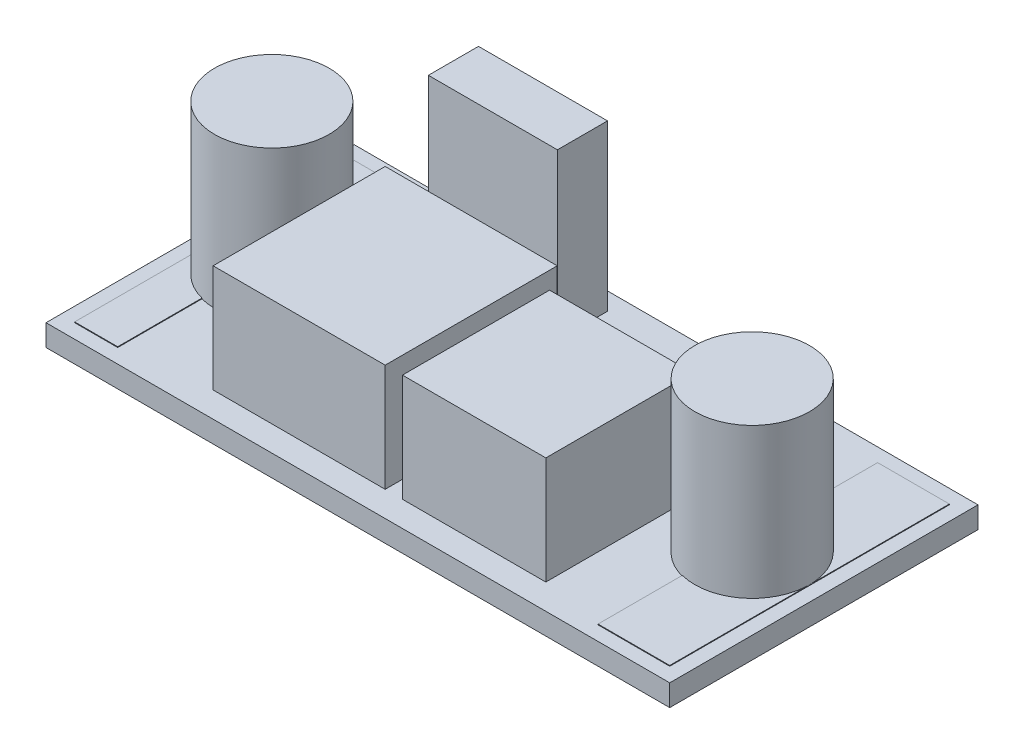
SolidWorks part; units mm, degrees
ref_plane "Спереди" through (0, 0, 0) normal (0, 0, 1) x (1, 0, 0)
ref_plane "Сверху" through (0, 0, 0) normal (0, 1, 0) x (1, 0, 0)
ref_plane "Справа" through (0, 0, 0) normal (1, 0, 0) x (0, 0, -1)
sketch "Эскиз1" plane through (0, 0, 0) normal (0, 1, 0) x (1, 0, 0)
  line L1 (0, 10.75) -> (-43.5, 10.75)
  line L2 (0, 10.75) -> (0, -10.75)
  line L3 (0, -10.75) -> (-43.5, -10.75)
  line L4 (-43.5, 10.75) -> (-43.5, -10.75)
  point P4 (0, 0)
  dimension "D1" = 21.5
  dimension "D2" = 43.5
extrude "Бобышка-Вытянуть1" add sketch "Эскиз1" along normal blind 1.5
sketch "Эскиз6" plane through (0, 0, 0) normal (0, 1, 0) x (1, 0, 0)
  line L0 (-43.5, -10.75) -> (0, -10.75) construction
  line L1 (0, 10.75) -> (-7, 10.75) construction
  line L2 (0, 10.75) -> (0, -10.75) construction
  line L3 (0, -10.75) -> (-7, -10.75) construction
  line L4 (-7, 10.75) -> (-7, -10.75) construction
  line L5 (-1, 9.75) -> (-6, 9.75)
  line L6 (-43.5, 10.75) -> (-38.5, 10.75) construction
  line L7 (-43.5, 10.75) -> (-43.5, -10.75) construction
  line L8 (-43.5, -10.75) -> (-38.5, -10.75) construction
  line L9 (-38.5, 10.75) -> (-38.5, -10.75) construction
  line L10 (-6, 9.75) -> (-6, -9.75)
  line L11 (-1, -9.75) -> (-6, -9.75)
  line L12 (-1, 9.75) -> (-1, -9.75)
  line L13 (-42.5, 9.75) -> (-39.5, 9.75)
  line L14 (-39.5, 9.75) -> (-39.5, -9.75)
  line L15 (-42.5, -9.75) -> (-39.5, -9.75)
  line L16 (-42.5, 9.75) -> (-42.5, -9.75)
  dimension "D1" = 7
  dimension "D2" = 5
  dimension "D3" = 1
extrude "Бобышка-Вытянуть4" add sketch "Эскиз6" along normal offset from surface (1.55 mm away) 0.05 up to face at (-21.75, 1.5, 0) offset beyond the face yes
sketch "Эскиз4" plane through (0, 0, 0) normal (0, 1, 0) x (1, 0, 0)
  line L9 (0, 0) -> (-43.5, 0) construction
  line L10 (-43.5, 10.75) -> (-43.5, -10.75) construction
  line L15 (-33.6103, 9.5227) -> (-24.6103, 9.5227)
  line L16 (-33.6103, 3.0151) -> (-21.6103, 3.0151)
  line L17 (-33.6103, 3.0151) -> (-33.6103, -8.9849)
  line L18 (-33.6103, -8.9849) -> (-21.6103, -8.9849)
  line L19 (-21.6103, 3.0151) -> (-21.6103, -8.9849)
  line L20 (-20.4056, 1.2772) -> (-10.4056, 1.2772)
  line L21 (-20.4056, 1.2772) -> (-20.4056, -8.9849)
  line L22 (-20.4056, -8.9849) -> (-10.4056, -8.9849)
  line L23 (-10.4056, 1.2772) -> (-10.4056, -8.9849)
  line L24 (-33.6103, 9.5227) -> (-33.6103, 6.0273)
  line L25 (-33.6103, 6.0273) -> (-24.6103, 6.0273)
  line L26 (-24.6103, 9.5227) -> (-24.6103, 6.0273)
  line L28 (-1, -9.75) -> (-1, 9.75) construction
  line L29 (-42.5, 9.75) -> (-42.5, -9.75) construction
  circle A0 centre (-38.5, 0) radius 4
  circle A1 centre (-5, 0) radius 4
  point P17 (0, 0)
  point P22 (0, 0)
  point P25 (-1, 0)
  point P26 (-1, 0)
  point P27 (-42.5, 0)
  point P28 (-42.5, 0)
  point P32 (-38.5, 0)
  dimension "D4" = 8
  dimension "D1" = 12
  dimension "D2" = 9
  dimension "D3" = 10
extrude "Бобышка-Вытянуть3" add sketch "Эскиз4" along normal blind 9 contours L18 L19 L16 L17 | L22 L23 L20 L21
sketch "Эскиз5" plane through (0, 0, 0) normal (0, 1, 0) x (1, 0, 0)
  line L0 (-43.5, 0) -> (0, 0)
  line L1 (-43.5, 10.75) -> (-43.5, -10.75) construction
extrude "Бобышка-Вытянуть5" add sketch "Эскиз4<2>" along normal blind 13 separate body contours L25 L26 L15 L24
sketch "Эскиз4<2>" plane through (0, 0, 0) normal (0, 1, 0) x (1, 0, 0) same geometry as "Эскиз4"
extrude "Бобышка-Вытянуть6" add sketch "Эскиз4<3>" along normal blind 12 separate body contours A1 | A0
sketch "Эскиз4<3>" plane through (0, 0, 0) normal (0, 1, 0) x (1, 0, 0) same geometry as "Эскиз4"
